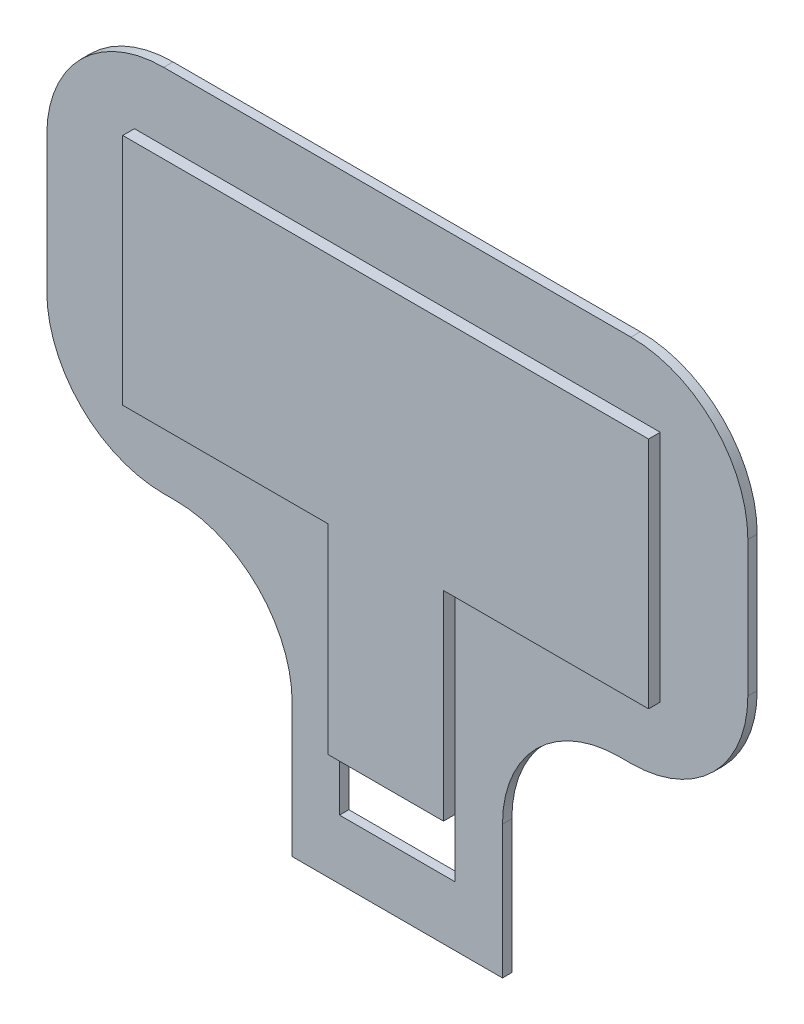
SolidWorks part; units mm, degrees
ref_plane "Front Plane" through (0, 0, 0) normal (0, 0, 1) x (1, 0, 0)
ref_plane "Top Plane" through (0, 0, 0) normal (0, 1, 0) x (1, 0, 0)
ref_plane "Right Plane" through (0, 0, 0) normal (1, 0, 0) x (0, 0, -1)
sketch "Sketch1" plane through (0, 0, 0) normal (0, 0, 1) x (1, 0, 0)
  line L1 (0, 0) -> (60, 0)
  line L2 (0, 0) -> (0, 53)
  line L3 (0, 53) -> (60, 53)
  line L4 (60, 0) -> (60, 53)
  dimension "D1" = 53
  dimension "D2" = 60
extrude "Boss-Extrude1" add sketch "Sketch1" along normal blind 0.8
sketch "Sketch2" plane through (0, 0, 0.8) normal (0, 0, 1) x (1, 0, 0)
  line L0 (60, 0) -> (60, 53) construction
  line L1 (10, 53) -> (50, 53)
  line L2 (0, 43) -> (0, 31.4)
  line L3 (10, 21.4) -> (11, 21.4)
  line L4 (60, 43) -> (60, 31.4)
  line L5 (0, 0) -> (60, 0) construction
  line L6 (21, 0) -> (39, 0)
  line L7 (21, 0) -> (21, 11.4)
  line L9 (39, 0) -> (39, 11.4)
  line L11 (49, 21.4) -> (50, 21.4)
  line L13 (0, 53) -> (60, 53)
  line L14 (0, 53) -> (0, 0)
  line L15 (0, 0) -> (60, 0)
  line L16 (60, 53) -> (60, 0)
  arc A0 (0, 31.4) -> (10, 21.4) centre (10, 31.4) ccw
  arc A1 (10, 53) -> (0, 43) centre (10, 43) ccw
  arc A2 (50, 53) -> (60, 43) centre (50, 43) cw
  arc A3 (50, 21.4) -> (60, 31.4) centre (50, 31.4) ccw
  arc A4 (21, 11.4) -> (11, 21.4) centre (11, 11.4) ccw
  arc A5 (49, 21.4) -> (39, 11.4) centre (49, 11.4) ccw
  point P13 (30, 0)
  point P14 (30, 53)
  point P17 (0, 21.4)
  point P20 (0, 53)
  point P25 (60, 21.4)
  point P30 (39, 21.4)
  line M5 (0, 53) -> (0, 0)
  line M6 (0, 0) -> (60, 0)
  line M7 (60, 0) -> (60, 53)
  line M8 (60, 53) -> (0, 53)
  dimension "D4" = 10
  dimension "D1" = 18
  dimension "D3" = 31.6
extrude "Cut-Extrude2" cut sketch "Sketch2" against normal blind 0.8 contours A1 M8 M5 | L7 A4 L3 A0 M5 M6 | L11 A5 L9 A3 M6 M7 | A2 M8 M7 region at (2.2337, 50.7663, 0.8) region at (57.7663, 50.7663, 0.8) region at (9.7105, 10.9133, 0.8) region at (50.2895, 10.9133, 0.8)
sketch "Sketch3" plane through (0, 0, 0.8) normal (0, 0, 1) x (1, 0, 0)
  line L0 (60, 31.4) -> (60, 43) construction
  line L1 (25.05, 5.1) -> (34.95, 5.1)
  line L2 (25.05, 5.1) -> (25.05, 27.2)
  line L3 (25.05, 27.2) -> (34.95, 27.2)
  line L4 (34.95, 5.1) -> (34.95, 27.2)
  line L6 (7.5, 47.2) -> (52.5, 47.2)
  line L7 (7.5, 47.2) -> (7.5, 27.2)
  line L8 (7.5, 27.2) -> (52.5, 27.2)
  line L9 (52.5, 47.2) -> (52.5, 27.2)
  line L10 (50, 53) -> (10, 53) construction
  line L12 (21, 0) -> (39, 0) construction
  point P10 (30, 27.2)
  point P14 (60, 37.2)
  point P15 (52.5, 37.2)
  point P18 (30, 53)
  point P19 (30, 47.2)
  line M18 (21, 0) -> (39, 0)
  dimension "D1" = 9.9
  dimension "D3" = 20
  dimension "D4" = 45
  dimension "D7" = 0
  dimension "D8" = 5.1
extrude "Boss-Extrude2" add sketch "Sketch3" along normal blind 1 contours L9 L6 L7 L8 L3 | L4 L3 L2 M18 region at (30, 16.15, 0.8) region at (30, 37.2, 0.8)
sketch "Sketch4" plane through (0, 0, 1.8) normal (0, 0, 1) x (1, 0, 0)
  line L0 (34.95, 5.1) -> (34.95, 27.2) construction
  line L1 (25.05, 5.1) -> (34.95, 5.1)
  line L2 (25.05, 5.1) -> (25.05, 10.1)
  line L3 (25.05, 10.1) -> (34.95, 10.1)
  line L4 (34.95, 5.1) -> (34.95, 10.1)
  dimension "D1" = 5
extrude "Cut-Extrude3" cut sketch "Sketch4" against normal blind 10
